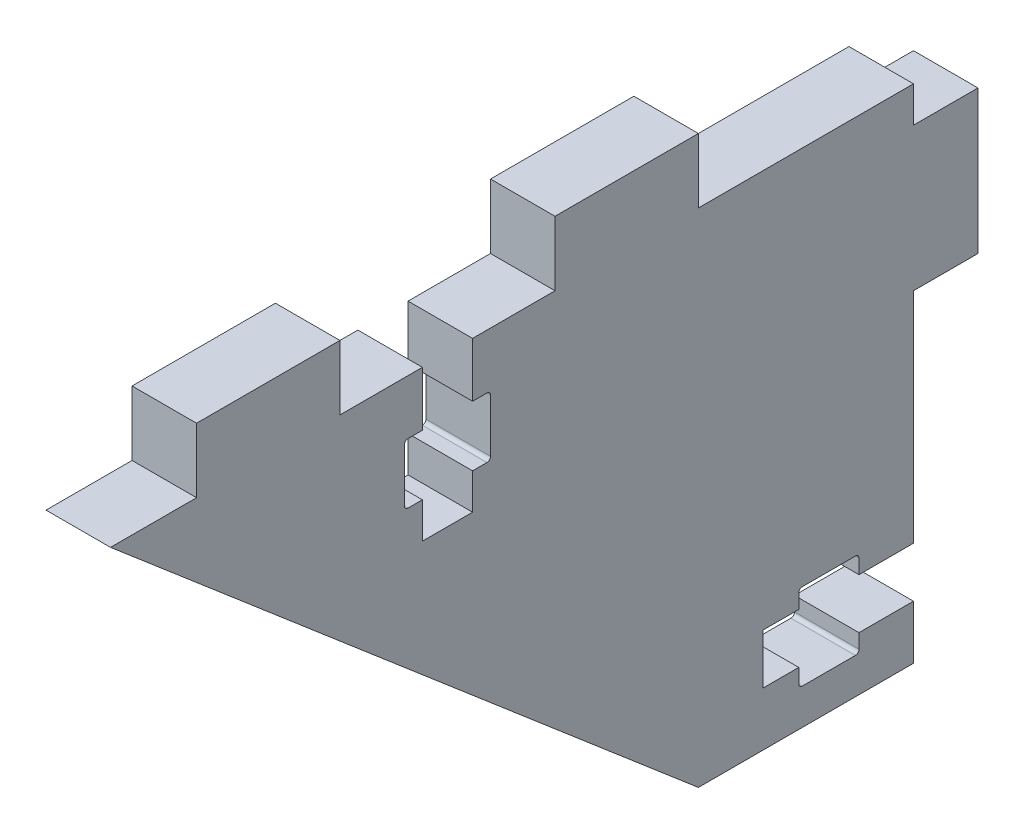
SolidWorks part; units mm, degrees
ref_plane "Front Plane" through (0, 0, 0) normal (0, 0, 1) x (1, 0, 0)
ref_plane "Top Plane" through (0, 0, 0) normal (0, 1, 0) x (1, 0, 0)
ref_plane "Right Plane" through (0, 0, 0) normal (1, 0, 0) x (0, 0, -1)
sketch "Sketch1" plane through (0, 0, 0) normal (1, 0, 0) x (0, 0, -1)
  line L0 (0, 0) -> (0, -35)
  line L1 (0, -35) -> (-56, 0)
  line L2 (-56, 0) -> (0, 0)
  dimension "D1" = 35
  dimension "D2" = 56
extrude "Boss-Extrude1" add sketch "Sketch1" along normal blind 4.5
sketch "Sketch2" plane through (4.5, 0, 0) normal (1, 0, 0) x (0, 0, -1)
  line L0 (0, -35) -> (0, 0) construction
  line L1 (-4.5, -2.5) -> (4.5, -2.5)
  line L2 (-4.5, -2.5) -> (-4.5, -12.5)
  line L3 (-4.5, -12.5) -> (4.5, -12.5)
  line L4 (4.5, -2.5) -> (4.5, -12.5)
  line L5 (-4.5, -2.5) -> (4.5, -12.5) construction
  line L6 (-4.5, -12.5) -> (4.5, -2.5) construction
  line L7 (0, 0) -> (-56, 0) construction
  point P0 (0, -7.5)
  dimension "D2" = 7.5
  dimension "D3" = 4.5
extrude "Boss-Extrude2" add sketch "Sketch2" against normal through all
sketch "Sketch3" plane through (4.5, 0, 0) normal (1, 0, 0) x (0, 0, -1)
  line L0 (0, -35) -> (-15, -35)
  line L1 (0, -25) -> (-56, 0)
  line L4 (0, -35) -> (0, -12.5) construction
  line L5 (0, -25) -> (0, -35)
  line L6 (-56, 0) -> (-15, -35)
  dimension "D1" = 15
  dimension "D2" = 10
extrude "Boss-Extrude3" add sketch "Sketch3" against normal through all
sketch "Sketch4" plane through (4.5, 0, 0) normal (1, 0, 0) x (0, 0, -1)
  line L0 (0, -29.5) -> (-10.5, -29.5) construction
  line L1 (0, -35) -> (0, -12.5) construction
  line L2 (0, -27.75) -> (-10.5, -27.75) construction
  line L3 (-10.5, -27.75) -> (-10.5, -31.25) construction
  line L4 (0, -31.25) -> (0, -27.75)
  line L5 (0, -27.75) -> (-3.8, -27.75)
  line L6 (-3.8, -27.75) -> (-3.8, -26.75)
  line L7 (-4.05, -26.5) -> (-7.75, -26.5)
  line L8 (-8, -26.75) -> (-8, -27.75)
  line L9 (-8, -27.75) -> (-10.5, -27.75)
  line L10 (-10.5, -27.75) -> (-10.5, -31.25)
  line L12 (0, -31.25) -> (-10.5, -31.25) construction
  line L13 (-8, -31.25) -> (-10.5, -31.25)
  line L14 (-8, -32.25) -> (-8, -31.25)
  line L15 (-4.05, -32.5) -> (-7.75, -32.5)
  line L16 (-3.8, -31.25) -> (-3.8, -32.25)
  line L17 (0, -31.25) -> (-3.8, -31.25)
  line L18 (4.5, -12.5) -> (4.5, -2.5) construction
  line L19 (0, -18.5) -> (-34.3286, -18.5) construction
  line L20 (-56, 0) -> (-15, -35) construction
  line L37 (0, -31.25) -> (-10.5, -31.25) construction
  arc A0 (-8, -32.25) -> (-7.75, -32.5) centre (-7.75, -32.25) ccw
  arc A1 (-4.05, -32.5) -> (-3.8, -32.25) centre (-4.05, -32.25) ccw
  arc A2 (-3.8, -26.75) -> (-4.05, -26.5) centre (-4.05, -26.75) ccw
  arc A3 (-7.75, -26.5) -> (-8, -26.75) centre (-7.75, -26.75) ccw
  point P10 (4.5, -7.5)
  point P20 (-8, -32.5)
  point P23 (-3.8, -32.5)
  point P26 (-3.8, -26.5)
  point P29 (-8, -26.5)
  dimension "D7" = 0.25
  dimension "D1" = 10.5
  dimension "D2" = 1.75
  dimension "D3" = 3
  dimension "D4" = 4.2
  dimension "D5" = 8
  dimension "D6" = 22
extrude "Cut-Extrude1" cut sketch "Sketch4" against normal through all
sketch "Sketch5" plane through (4.5, 0, 0) normal (1, 0, 0) x (0, 0, -1)
  line L0 (0, 0) -> (-56, 0) construction
  line L1 (-25, 4.5) -> (-15, 4.5)
  line L2 (-25, 4.5) -> (-25, -4.5)
  line L3 (-25, -4.5) -> (-15, -4.5)
  line L4 (-15, 4.5) -> (-15, -4.5)
  line L5 (-25, 4.5) -> (-15, -4.5) construction
  line L6 (-25, -4.5) -> (-15, 4.5) construction
  line L7 (-32.5, 0) -> (-32.5, 4.5) construction
  line L8 (-40, -4.5) -> (-50, 4.5) construction
  line L9 (-40, 4.5) -> (-50, -4.5) construction
  line L10 (-50, 4.5) -> (-50, -4.5)
  line L11 (-40, -4.5) -> (-50, -4.5)
  line L12 (-40, 4.5) -> (-40, -4.5)
  line L13 (-40, 4.5) -> (-50, 4.5)
  line L14 (-25, -4.5) -> (-15, 4.5) construction
  point P0 (-20, 0)
  point P14 (-45, 0)
  dimension "D3" = 4.5
  dimension "D1" = 20
  dimension "D2" = 10
  dimension "D4" = 25
extrude "Boss-Extrude4" add sketch "Sketch5" against normal through all
sketch "Sketch6" plane through (4.5, 0, 0) normal (1, 0, 0) x (0, 0, -1)
  line L0 (-32.5, 0) -> (-32.5, -10.5) construction
  line L1 (-25, 0) -> (-40, 0) construction
  line L2 (-30.75, -10.5) -> (-34.25, -10.5) construction
  line L3 (-34.25, -10.5) -> (-34.25, 0) construction
  line L4 (-30.75, 0) -> (-34.25, 0)
  line L5 (-34.25, 0) -> (-34.25, -3.8)
  line L6 (-34.25, -3.8) -> (-35.25, -3.8)
  line L7 (-35.5, -4.05) -> (-35.5, -7.75)
  line L8 (-35.25, -8) -> (-34.25, -8)
  line L9 (-34.25, -8) -> (-34.25, -10.5)
  line L10 (-34.25, -10.5) -> (-30.75, -10.5)
  line L11 (-30.75, -10.5) -> (-30.75, 0) construction
  line L12 (-30.75, -8) -> (-30.75, -10.5)
  line L13 (-29.75, -8) -> (-30.75, -8)
  line L14 (-29.5, -4.05) -> (-29.5, -7.75)
  line L15 (-30.75, -3.8) -> (-29.75, -3.8)
  line L16 (-30.75, 0) -> (-30.75, -3.8)
  arc A0 (-35.5, -7.75) -> (-35.25, -8) centre (-35.25, -7.75) ccw
  arc A1 (-35.25, -3.8) -> (-35.5, -4.05) centre (-35.25, -4.05) ccw
  arc A2 (-29.75, -3.8) -> (-29.5, -4.05) centre (-29.75, -4.05) cw
  arc A3 (-29.5, -7.75) -> (-29.75, -8) centre (-29.75, -7.75) cw
  point P12 (-35.5, -8)
  point P15 (-35.5, -3.8)
  point P26 (-29.5, -3.8)
  point P27 (-29.5, -8)
  dimension "D1" = 10.5
  dimension "D2" = 1.75
  dimension "D4" = 4.2
  dimension "D6" = 0.25
  dimension "D3" = 8
  dimension "D5" = 3
extrude "Cut-Extrude2" cut sketch "Sketch6" against normal through all
equation "\"X-ROD-SPACING\"=45"
equation "\"Y-ROD-SPACING\"=75"
equation "\"Z-ROD-SPACING\"=17.5"
equation "\"Y-BED-OFFSET\"=2"
equation "\"Y-BED-ROD-INSET\"=3.5"
equation "\"Y-BED-SCREW-SPACING\"=209"
equation "\"Y-BED-SCREW-CUTOUT-SLOT-HEIGHT\"=1"
equation "\"T-SLOT-NUT-FILLET-RADIUS\"=0.25"
equation "\"T-SLOT-SCREW-SHAFT-RADIUS\"=1.75"
equation "\"T-SLOT-SCREW-SHAFT-CUTOUT-LENGTH\"=10.5"
equation "\"T-SLOT-NUT-DEPTH\"=4.2"
equation "\"T-SLOT-NUT-WIDTH\"=3"
equation "\"T-SLOT-NUT-END-DISTANCE\"=8"
equation "\"ACRYLIC-THICKNESS\"=10"
equation "\"ACRYLIC-THICKNESS2\"=4.5"
equation "\"ACRYLIC-TAB-CUTOUT-SIZE\"=\"ACRYLIC-THICKNESS\"+\"ACRYLIC-TAB-TOLERANCE\"*2"
equation "\"ACRYLIC-TAB-WIDTH\"=\"ACRYLIC-THICKNESS\""
equation "\"ACRYLIC-M3-HOLE\"=3.2"
equation "\"SMOOTHROD-CAP-SCREW-DISTANCE\"=20"
equation "\"FRAME-WIDTH-INNER\"=370"
equation "\"NEMA17-HOLE-SPACING\"=31"
equation "\"NEMA17-CENTRAL-CUTOUT\"=22.5"
equation "\"Z-BRACKET-REACH\"=55"
equation "\"Z-ROD-INSET\"=16"
equation "\"TOP-BRACKET-SPACING\"=40"
equation "\"SMOOTHROD-X-LENGTH\"=350"
equation "\"SMOOTHROD-Y-LENGTH\"=350"
equation "\"SMOOTHROD-Z-LENGTH\"=350"
equation "\"SMOOTHROD-TIGHTENING-HEADROOM\"=1"
equation "\"LEADSCREW-Z-LENGTH\"=300"
equation "\"SCREW-LENGTH-FRAME\"=\"ACRYLIC-THICKNESS\" + 10"
equation "\"SCREW-LENGTH-MOTOR\"=\"ACRYLIC-THICKNESS\" + 5"
equation "\"SCREW-LENGTH-EXTRUDER\"=28"
equation "\"SCREW-HEAD-RADIUS\"=6"
equation "\"PRINTED-X-SMOOTHROD-DIAMETER\"=8.2"
equation "\"PRINTED-X-SMOOTHROD-CUTOUT\"=10"
equation "\"PRINTED-X-BASE-HEIGHT\"=10"
equation "\"PRINTED-LM8UU-CUTOUT-SIZE\"=16"
equation "\"PRINTED-LM8UU-CUTOUT-LENGTH\"=24.5"
equation "\"PRINTED-X-IDLER-HEIGHT\"=16"
equation "\"PSU-MOUNTING-WIDTH\"=95"
equation "\"PSU-MOUNTING-HEIGHT\"=177"
equation "\"Y-BELT-TO-ROD-DISTANCE\"=20"
equation "\"SPOOL-HOLDER-ROD-SPACING\"=150"
equation "\"ACRYLIC-X-CARRIAGE-WIDTH\"=55"
equation "\"ACRYLIC-X-CARRIAGE-HEIGHT\"=75"
equation "\"ACRYLIC-X-CARRIAGE-SCREW-SPACING-X\"=15"
equation "\"ACRYLIC-X-CARRIAGE-SCREW-SPACING-Y\"=33"
equation "\"ACRYLIC-X-CARRIAGE-CENTER-TAB-SPACING\"=14"
equation "\"ACRYLIC-X-CARRIAGE-EXTRUDER-SHELF-DEPTH\"=\"ACRYLIC-X-CARRIAGE-EXTRUDER-OFFSET\" + 30"
equation "\"D2@Sketch1\"=\"ACRYLIC-X-CARRIAGE-EXTRUDER-SHELF-DEPTH\""
equation "\"D1@Boss-Extrude1\"=\"ACRYLIC-THICKNESS2\""
equation "\"D1@Sketch2\"=\"ACRYLIC-TAB-WIDTH\""
equation "\"D3@Sketch2\"=\"ACRYLIC-THICKNESS2\""
equation "\"ACRYLIC-X-CARRIAGE-LM8UU-CUTOUT-WIDTH\"=24.25"
equation "\"ACRYLIC-X-CARRIAGE-EXTRUDER-BRACE-SPACING\"=23"
equation "\"ACRYLIC-X-CARRIAGE-EXTRUDER-BRACE-HEIGHT\"=35"
equation "\"D1@Sketch1\"=\"ACRYLIC-X-CARRIAGE-EXTRUDER-BRACE-HEIGHT\""
equation "\"D1@Sketch4\"=\"T-SLOT-SCREW-SHAFT-CUTOUT-LENGTH\""
equation "\"D2@Sketch4\"=\"T-SLOT-SCREW-SHAFT-RADIUS\""
equation "\"D3@Sketch4\"=\"T-SLOT-NUT-WIDTH\""
equation "\"D4@Sketch4\"=\"T-SLOT-NUT-DEPTH\""
equation "\"D5@Sketch4\"=\"T-SLOT-NUT-END-DISTANCE\""
equation "\"D7@Sketch4\"=\"T-SLOT-NUT-FILLET-RADIUS\""
equation "\"ACRYLIC-X-CARRIAGE-EXTRUDER-BRACE-SCREW-SPACING\"=22"
equation "\"D6@Sketch4\"=\"ACRYLIC-X-CARRIAGE-EXTRUDER-BRACE-SCREW-SPACING\""
equation "\"ACRYLIC-X-CARRIAGE-EXTRUDER-BRACE-TAB-OFFSET\"=20"
equation "\"D1@Sketch5\"=\"ACRYLIC-X-CARRIAGE-EXTRUDER-BRACE-TAB-OFFSET\""
equation "\"D2@Sketch5\"=\"ACRYLIC-TAB-WIDTH\""
equation "\"D3@Sketch5\"=\"ACRYLIC-THICKNESS2\""
equation "\"ACRYLIC-X-CARRIAGE-EXTRUDER-OFFSET\"=26"
equation "\"ACRYLIC-X-CARRIAGE-EXTRUDER-ANGLE\"=90"
equation "\"D1@Sketch6\"=\"T-SLOT-SCREW-SHAFT-CUTOUT-LENGTH\""
equation "\"D2@Sketch6\"=\"T-SLOT-SCREW-SHAFT-RADIUS\""
equation "\"D3@Sketch6\"=\"T-SLOT-NUT-END-DISTANCE\""
equation "\"D4@Sketch6\"=\"T-SLOT-NUT-DEPTH\""
equation "\"D5@Sketch6\"=\"T-SLOT-NUT-WIDTH\""
equation "\"D6@Sketch6\"=\"T-SLOT-NUT-FILLET-RADIUS\""
